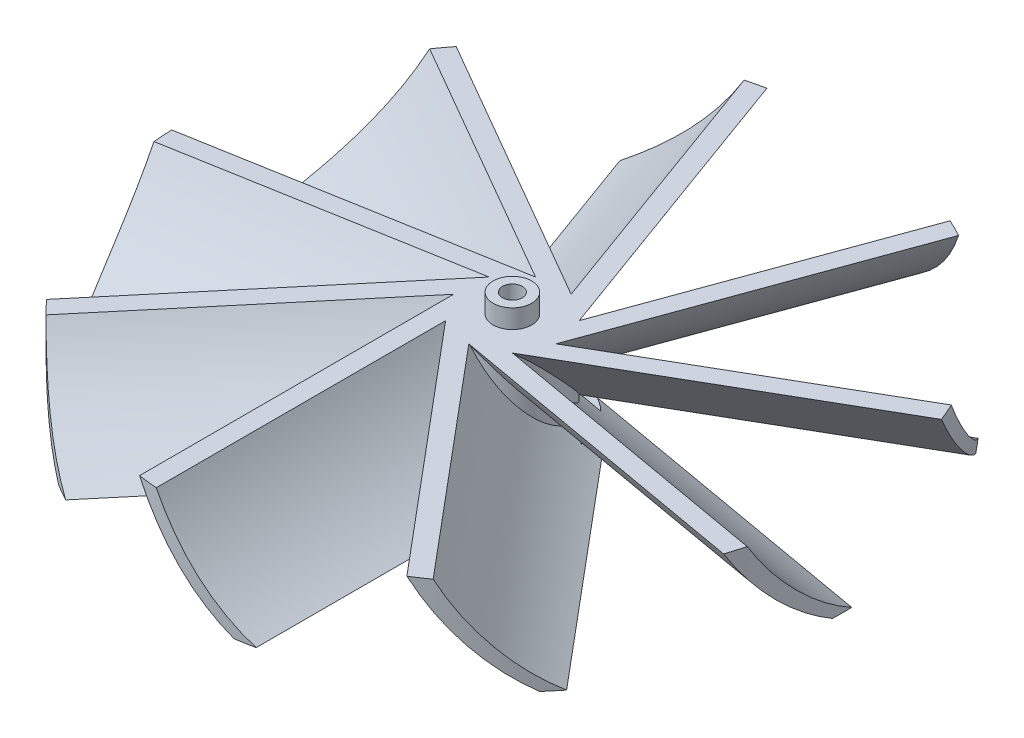
SolidWorks part; units mm, degrees
ref_plane "Front Plane" through (0, 0, 0) normal (0, 0, 1) x (1, 0, 0)
ref_plane "Top Plane" through (0, 0, 0) normal (0, 1, 0) x (1, 0, 0)
ref_plane "Right Plane" through (0, 0, 0) normal (1, 0, 0) x (0, 0, -1)
sketch "Sketch1" plane through (0, 0, 0) normal (0, 1, 0) x (1, 0, 0)
  circle A0 centre (0, 0) radius 5
  dimension "D1" = 10
extrude "Boss-Extrude1" add sketch "Sketch1" along normal blind 5 and the other way blind 5
sketch "Sketch2" plane through (0, 0, 0) normal (0, 0, 1) x (1, 0, 0)
  line L0 (5, 5) -> (-5, 5) construction
  line L1 (-5, 0.8212) -> (5.0825, -5) construction
  line L2 (-4.9175, 5) -> (0.856, -5) construction
  line L3 (-5, 5) -> (5, 5) construction
  line L4 (-5, -5) -> (-5, 5) construction
  line L5 (-5, -5) -> (5, -5) construction
  line L6 (5, 5) -> (5, -5) construction
  line L7 (-5, -5) -> (5, -5) construction
  line L8 (18.7428, 18.6603) -> (20.7428, 18.6603) construction
  line L9 (-4.9175, 5) -> (-2.9175, 5)
  line L10 (7.0825, -5) -> (5.0825, -5)
  line L11 (5, -5) -> (5, 5) construction
  line L12 (-5, 5) -> (-5, -5) construction
  line L13 (-4.9175, 5) -> (-4.9175, -5) construction
  line L15 (7.0825, 5) -> (7.0825, -5) construction
  arc A0 (-4.9175, 5) -> (5.0825, -5) centre (18.7428, 18.6603) ccw
  arc A1 (-2.9175, 5) -> (7.0825, -5) centre (20.7428, 18.6603) ccw
  dimension "D4" = 2
  dimension "D2" = 30
  dimension "D3" = 60
  dimension "D6" = 12
extrude "Boss-Extrude2" add sketch "Sketch2" along normal blind 45 contours A1 L10 A0 L9
sketch "Sketch3" plane through (0, 0, 0) normal (0, 0, 1) x (1, 0, 0)
  line L0 (0, 0) -> (0, 49.4452) construction
pattern_circular "CirPattern1" count 9 every 40 about axis through (0, 0, 0) along (0, 1, 0) of "Boss-Extrude2"
sketch "Sketch4" plane through (0, 5, 0) normal (0, 1, 0) x (1, 0, 0)
  circle A0 centre (0, 0) radius 35
  circle A1 centre (0, 0) radius 135
  dimension "D1" = 100
  dimension "D2" = 70
extrude "Cut-Extrude1" cut sketch "Sketch4" against normal blind 45
sketch "Sketch5" plane through (0, -5, 0) normal (0, -1, 0) x (1, 0, 0)
  line L1 (0, 0) -> (0, 7.5) construction
  line L2 (-0.625, -0.995) -> (-0.625, 0.995)
  circle A0 centre (0, 0) radius 7.5 construction
  arc A1 (-0.625, -0.995) -> (-0.625, 0.995) centre (0, 0) ccw
  point P8 (1.175, 0)
  dimension "D1" = 15
  dimension "D3" = 2.35
  dimension "D4" = 1.8
extrude "Cut-Extrude2" cut sketch "Sketch5" against normal blind 5 contours A1 L2
sketch "Sketch6" plane through (0, -5, 0) normal (0, -1, 0) x (1, 0, 0)
  circle A0 centre (0, 0) radius 6.6348
  circle A1 centre (0, 0) radius 5
extrude "Boss-Extrude3" add sketch "Sketch6" against normal blind 1
sketch "Sketch7" plane through (0, 5, 0) normal (0, 1, 0) x (1, 0, 0)
  circle A0 centre (0, 0) radius 1.05
  circle A1 centre (0, 0) radius 2.05
  dimension "D1" = 2.1
  dimension "D2" = 4.1
extrude "Boss-Extrude4" add sketch "Sketch7" along normal blind 2
sketch "Sketch8" plane through (0, 5, 0) normal (0, 1, 0) x (1, 0, 0)
  circle A0 centre (0, 0) radius 1.05
extrude "Cut-Extrude3" cut sketch "Sketch8" against normal blind 2
